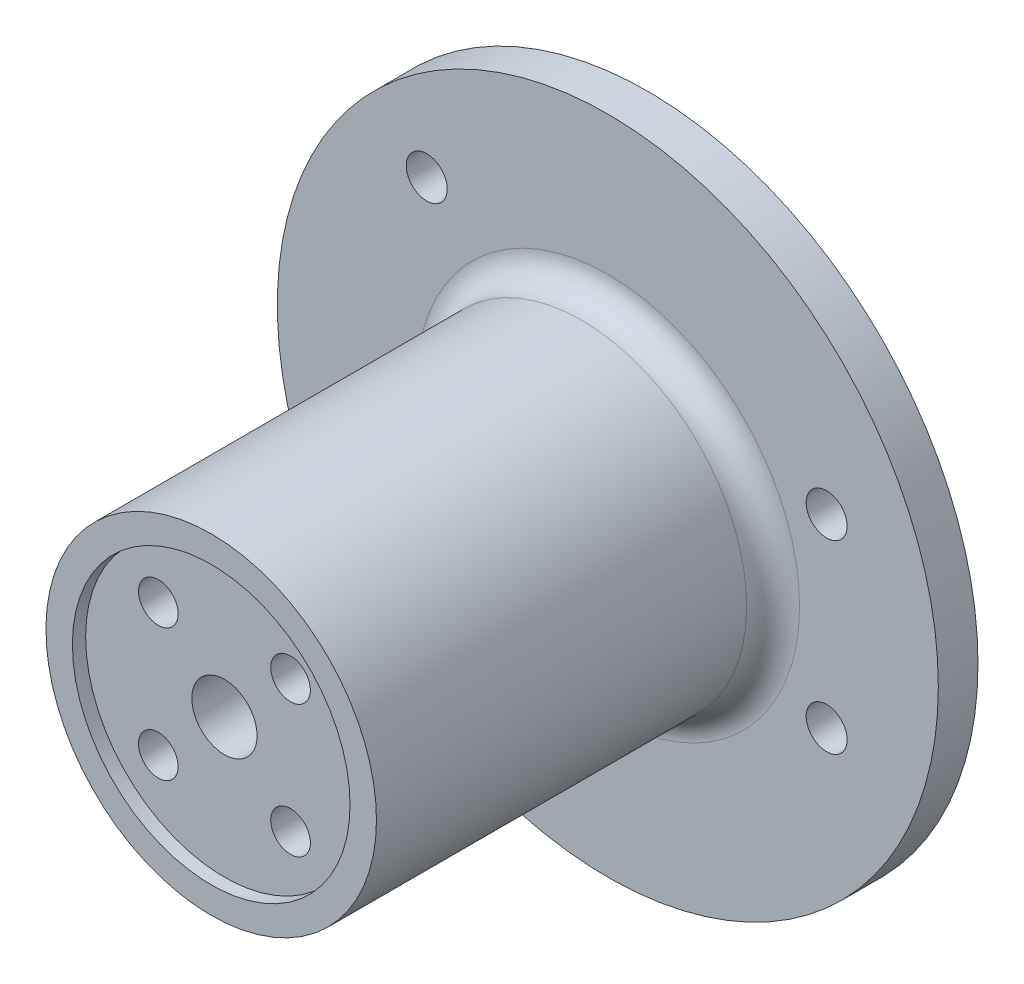
SolidWorks part; units mm, degrees
ref_plane "前视基准面" through (0, 0, 0) normal (0, 0, 1) x (1, 0, 0)
ref_plane "上视基准面" through (0, 0, 0) normal (0, 1, 0) x (1, 0, 0)
ref_plane "右视基准面" through (0, 0, 0) normal (1, 0, 0) x (0, 0, -1)
other "Configuration Table"
ref_plane "基准面1" through (0, 0, 0.0483) normal (0, 0, 1) x (1, 0, 0)
sketch "草图2" plane through (0, 0, 0.0483) normal (0, 0, 1) x (1, 0, 0)
  circle A0 centre (-1.0507, -17) radius 25
  circle A1 centre (-14.75, -3) radius 1.55
  circle A2 centre (-14.75, -17) radius 1.55
  circle A3 centre (-14.75, -31) radius 1.55
  circle A4 centre (15.5, -23.95) radius 1.55
  circle A5 centre (15.5, -9.95) radius 1.55
  dimension "D1" = 50
extrude "凸台-拉伸1" add sketch "草图2" along normal blind 3
sketch "草图3" plane through (0, 0, 3.0483) normal (0, 0, 1) x (1, 0, 0)
  circle A1 centre (-1.0507, -17) radius 12.5
extrude "凸台-拉伸2" add sketch "草图3" along normal blind 30
sketch "草图4" plane through (0, 0, 0.0483) normal (0, 0, -1) x (-1, 0, 0)
  line L1 (-3.9493, -12) -> (6.0507, -12)
  line L2 (-3.9493, -12) -> (-3.9493, -22)
  line L3 (-3.9493, -22) -> (6.0507, -22)
  line L4 (6.0507, -12) -> (6.0507, -22)
  line L5 (-3.9493, -12) -> (6.0507, -22) construction
  line L6 (-3.9493, -22) -> (6.0507, -12) construction
  circle A0 centre (1.0507, -17) radius 10.5
  circle A1 centre (1.0507, -17) radius 4
  circle A2 centre (6.0507, -12) radius 2.5
  circle A3 centre (6.0507, -22) radius 2.5
  circle A4 centre (-3.9493, -12) radius 2.5
  circle A5 centre (-3.9493, -22) radius 2.5
  dimension "D1" = 21
  dimension "D2" = 8
  dimension "D5" = 5
  dimension "D6" = 5
  dimension "D7" = 5
  dimension "D8" = 5
  dimension "D3" = 10
  dimension "D4" = 10
extrude "切除-拉伸1" cut sketch "草图4" against normal blind 18 contours L1 A2 L4 | L4 A2 L1 | L3 A3 L4 | L4 A3 L3 | L2 A5 L3 | L3 A5 L2 | L2 A4 L1 | L1 A4 L2 | A1 region at (4.303, -11.6463, 0.0483) region at (2.8882, -13.061, 0.0483) region at (-6.4044, -11.6463, 0.0483) region at (-4.9897, -13.061, 0.0483) region at (2.8882, -20.939, 0.0483) region at (4.303, -22.3537, 0.0483) region at (-6.4044, -22.3537, 0.0483) region at (-4.9897, -20.939, 0.0483) region at (-1.0507, -17, 0.0483)
sketch "草图5" plane through (0, 0, 0.0483) normal (0, 0, -1) x (-1, 0, 0)
  circle A0 centre (1.0507, -17) radius 2.467
  circle A1 centre (6.0507, -12) radius 1.5
  circle A2 centre (-3.9493, -12) radius 1.5
  circle A3 centre (-3.9493, -22) radius 1.5
  circle A4 centre (6.0507, -22) radius 1.5
  dimension "D1" = 3
  dimension "D2" = 3
  dimension "D3" = 3
  dimension "D4" = 3
extrude "切除-拉伸2" cut sketch "草图5" against normal blind 33
sketch "草图6" plane through (0, 0, 33.0483) normal (0, 0, 1) x (1, 0, 0)
  circle A0 centre (-1.0507, -17) radius 10.5
  dimension "D1" = 21
extrude "切除-拉伸3" cut sketch "草图6" against normal blind 1
fillet "圆角1" radius 2 1 edges at (11.4493, -17, 3.0483) type face fillet first side face at (11.4493, -17, 33.0483) second side face at (-2.4254, -17, 3.0483)
